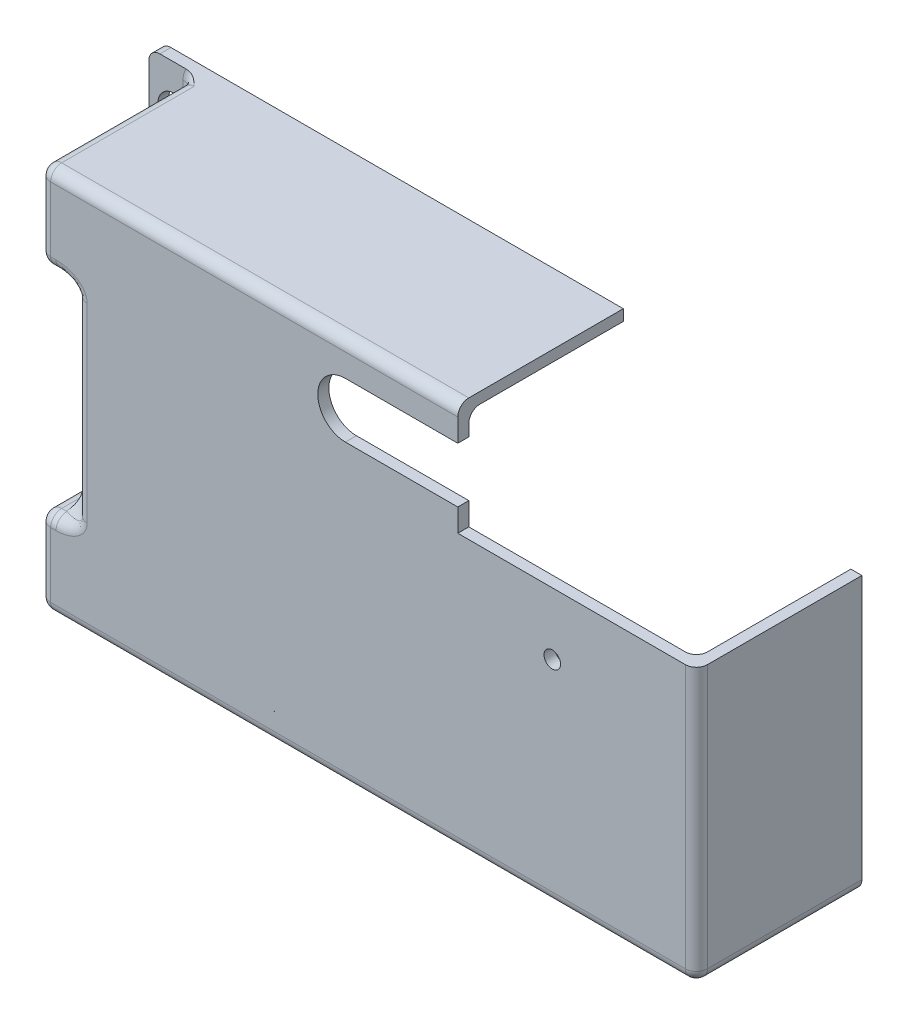
SolidWorks part; units mm, degrees
material "3D_printed_PLA"
ref_plane "Front Plane" through (0, 0, 0) normal (0, 0, 1) x (1, 0, 0)
ref_plane "Top Plane" through (0, 0, 0) normal (0, 1, 0) x (1, 0, 0)
ref_plane "Right Plane" through (0, 0, 0) normal (1, 0, 0) x (0, 0, -1)
sketch "Sketch1" plane through (0, 0, 0) normal (0, 0, 1) x (1, 0, 0)
  line L1 (-63.625, -35) -> (63.625, -35)
  line L2 (-63.625, -35) -> (-63.625, 35)
  line L3 (-63.625, 35) -> (63.625, 35)
  line L4 (63.625, -35) -> (63.625, 35)
  line L5 (-63.625, -35) -> (63.625, 35) construction
  line L6 (-63.625, 35) -> (63.625, -35) construction
  point P0 (0, 0)
  dimension "D1" = 127.25
  dimension "D2" = 70
extrude "Boss-Extrude1" add sketch "Sketch1" along normal blind 2
sketch "Sketch2" plane through (0, 0, 0) normal (0, 0, -1) x (-1, 0, 0)
  line L0 (-61.625, 33) -> (-61.625, -33)
  line L1 (-61.625, -33) -> (61.625, -33)
  line L2 (61.625, -33) -> (61.625, 33)
  line L3 (61.625, 33) -> (-61.625, 33)
  line L4 (-63.625, 35) -> (-63.625, -35)
  line L5 (-63.625, -35) -> (63.625, -35)
  line L6 (63.625, -35) -> (63.625, 35)
  line L7 (63.625, 35) -> (-63.625, 35)
  line L8 (-63.625, 35) -> (-63.625, -35)
  line L9 (-63.625, -35) -> (63.625, -35)
  line L10 (63.625, -35) -> (63.625, 35)
  line L11 (63.625, 35) -> (-63.625, 35)
  dimension "D1" = 0
  dimension "D2" = 2
extrude "Boss-Extrude2" add sketch "Sketch2" along normal blind 28
sketch "Sketch5" plane through (0, 0, 2) normal (0, 0, 1) x (1, 0, 0)
  line L0 (-63.625, 19.25) -> (-45.625, 19.25)
  line L1 (-63.625, 35) -> (-63.625, -35) construction
  line L2 (-45.625, 19.25) -> (-45.625, 21.75)
  line L3 (-45.625, 21.75) -> (-54.625, 21.75)
  line L4 (-54.625, 21.75) -> (-54.625, 35)
  line L5 (63.625, 35) -> (-63.625, 35) construction
  line L6 (-54.625, 35) -> (-63.625, 35)
  line L7 (-63.625, 35) -> (-63.625, 19.25)
  line L8 (-61.625, 0) -> (-39.8001, 0) construction
  line L9 (-61.625, -33) -> (-61.625, 33) construction
  line L10 (-54.625, -35) -> (-63.625, -35)
  line L11 (-54.625, -21.75) -> (-54.625, -35)
  line L12 (-45.625, -21.75) -> (-54.625, -21.75)
  line L13 (-45.625, -19.25) -> (-45.625, -21.75)
  line L14 (-63.625, -19.25) -> (-45.625, -19.25)
  line L15 (-63.625, -35) -> (-63.625, -19.25)
  dimension "D1" = 15.75
  dimension "D2" = 18
  dimension "D3" = 2.5
  dimension "D4" = 9
extrude "Boss-Extrude3" add sketch "Sketch5" against normal offset from surface (29.75 mm away) 0.25 up to face at (0, 0, -28)
sketch "Sketch6" plane through (0, 0, 2) normal (0, 0, 1) x (1, 0, 0)
  line L0 (-61.625, -19.25) -> (-45.625, -19.25) construction
  line L1 (-45.625, 19.25) -> (-52.625, 19.25)
  line L2 (-45.625, 19.25) -> (-45.625, -19.25)
  line L3 (-45.625, -19.25) -> (-52.625, -19.25)
  line L4 (-52.625, 19.25) -> (-52.625, -19.25)
  dimension "D1" = 7
extrude "Boss-Extrude4" add sketch "Sketch6" against normal blind 5.75
sketch "Sketch7" plane through (-63.625, 0, 0) normal (-1, 0, 0) x (0, 0, 1)
  line L0 (2, 35) -> (2, -35) construction
  line L1 (2, -19.25) -> (-28, -19.25)
  line L2 (2, -19.25) -> (2, 19.25)
  line L3 (2, 19.25) -> (-28, 19.25)
  line L4 (-28, -19.25) -> (-28, 19.25)
  line L5 (-28, -35) -> (-28, 35) construction
  line L6 (-28, 35) -> (2, 0) construction
  line L7 (2, 0) -> (-28, -35) construction
  line L8 (0, 19.25) -> (-27.75, 19.25) construction
extrude "Cut-Extrude2" cut sketch "Sketch7" against normal up to vertex
sketch "Sketch8" plane through (0, -35, 0) normal (0, -1, 0) x (1, 0, 0)
  line L0 (63.625, -28) -> (-63.625, -28) construction
  line L1 (-63.625, 2) -> (-55.425, 2)
  line L2 (-63.625, 2) -> (-63.625, -26)
  line L3 (-63.625, -26) -> (-55.425, -26)
  line L4 (-55.425, 2) -> (-55.425, -26)
  line L5 (-54.625, 0) -> (-54.625, -27.75) construction
  dimension "D1" = 2
  dimension "D2" = 0.8
extrude "Cut-Extrude3" cut sketch "Sketch8" against normal through all both and the other way through all
chamfer "Chamfer1" distance 5 angle 45 1 edges at (-52.625, 0, 2)
fillet "Fillet1" radius 2 32 edges at (3.5, -33, 0) (61.625, 0, 0) (3.5, 33, 0) (4.1, -35, 2) (4.1, 35, 2) (63.625, 0, 2) (-61.625, 33, -27.875) (-61.625, -33, -27.875) (61.625, -33, -14) (61.625, 33, -14) (-63.625, 35, -27) (63.625, 35, -13) (63.625, -35, -13) (-63.625, -35, -27) (-54.625, -27.375, 0) (-54.625, 27.375, 0) (-50.125, 21.75, 0) (-45.625, 0, 0) (-50.125, -21.75, 0) (-55.425, 27.125, 2) (-55.425, -27.125, 2) (-51.525, -19.25, 2) (-47.625, 0, 2) (-51.525, 19.25, 2) (-63.625, -19.25, -27) (-63.625, 19.25, -27) (-55.425, 19.25, -12) (-55.425, -19.25, -12) (-50.125, -19.25, -0.5) (-50.125, 19.25, -0.5) (-55.425, -35, -12) (-55.425, 35, -12)
sketch "Sketch3" plane through (0, 0, 2) normal (0, 0, 1) x (1, 0, 0)
  line L0 (63.625, 33) -> (63.625, -33) construction
  line L1 (63.625, 14.75) -> (20.375, 14.75)
  line L2 (63.625, 14.75) -> (63.625, 35)
  line L3 (63.625, 35) -> (20.375, 35)
  line L4 (20.375, 14.75) -> (20.375, 35)
  line L5 (-53.425, 35) -> (61.625, 35) construction
  dimension "D1" = 43.25
  dimension "D2" = 20.25
extrude "Cut-Extrude1" cut sketch "Sketch3" against normal through all both and the other way through all
fillet "Fillet2" radius 2 6 edges at (-54.8392, -19.8358, -26) (-54.8392, -34.4142, -26) (-54.8392, 34.4142, -26) (-54.8392, 19.8358, -26) (-55.425, -27.125, -26) (-55.425, 27.125, -26)
sketch "Sketch9" plane through (0, 0, -26) normal (0, 0, 1) x (1, 0, 0)
  circle A0 centre (-58.9747, -27.125) radius 3
  circle A1 centre (-58.9747, 27.125) radius 3
  point P5 (0, 0)
  point P7 (0, 0)
  point P8 (-57.425, -27.125)
  point P9 (0, 0)
  point P10 (-58.9747, -27.125)
  point P11 (-59.0271, 27.125)
  point P12 (0, 0)
  dimension "D1" = 6
extrude "Cut-Extrude4" cut sketch "Sketch9" along normal through all and the other way blind 2.5
sketch "Sketch10" plane through (0, 0, -26) normal (0, 0, 1) x (1, 0, 0)
  line L0 (-63.625, 33) -> (-63.625, 21.25) construction
  line L1 (-63.625, -21.25) -> (-63.625, -33) construction
  circle A0 centre (-56.3911, 27.125) radius 1.5
  circle A1 centre (-56.3911, -27.125) radius 1.5
  point P6 (0, 0)
  point P7 (-42.5, -18.75)
  point P8 (0, 0)
  point P9 (-60.7059, -19.625)
  point P10 (0, 0)
  point P11 (-60.7059, 19.625)
  point P12 (-60.7059, -28.1572)
  point P13 (-60.7059, 26.9517)
  point P16 (-63.625, 27.125)
  point P19 (-63.625, -27.125)
  point P20 (-55.425, -27.125)
  point P21 (-57.425, -27.125)
  point P22 (0, 0)
  point P23 (-55.425, -27.125)
  point P24 (0, 0)
  point P25 (0, 0)
  point P26 (-55.425, -27.125)
  point P27 (-56.3911, -27.125)
  point P28 (-56.6281, -27.125)
  point P30 (0, 0)
  dimension "D1" = 3
extrude "Cut-Extrude5" cut sketch "Sketch10" along normal through all
sketch "Sketch11" plane through (0, 0, 2) normal (0, 0, 1) x (1, 0, 0)
  circle A0 centre (37.5, 3.5) radius 1.5 construction
  circle A1 centre (37.5, 3.5) radius 1.5
extrude "Cut-Extrude6" cut sketch "Sketch11" against normal through all both and the other way through all
sketch "Sketch12" plane through (0, 0, 2) normal (0, 0, 1) x (1, 0, 0)
  line L0 (20.375, 23.875) -> (0, 23.875) construction
  line L1 (20.375, 14.75) -> (20.375, 33) construction
  line L2 (20.375, 18.875) -> (0, 18.875)
  line L3 (20.375, 28.875) -> (0, 28.875)
  arc A0 (20.375, 18.875) -> (20.375, 28.875) centre (20.375, 23.875) ccw
  arc A1 (0, 28.875) -> (0, 18.875) centre (0, 23.875) ccw
  point P4 (10.1875, 23.875)
  dimension "D1" = 5
extrude "Cut-Extrude7" cut sketch "Sketch12" against normal through all both and the other way through all
